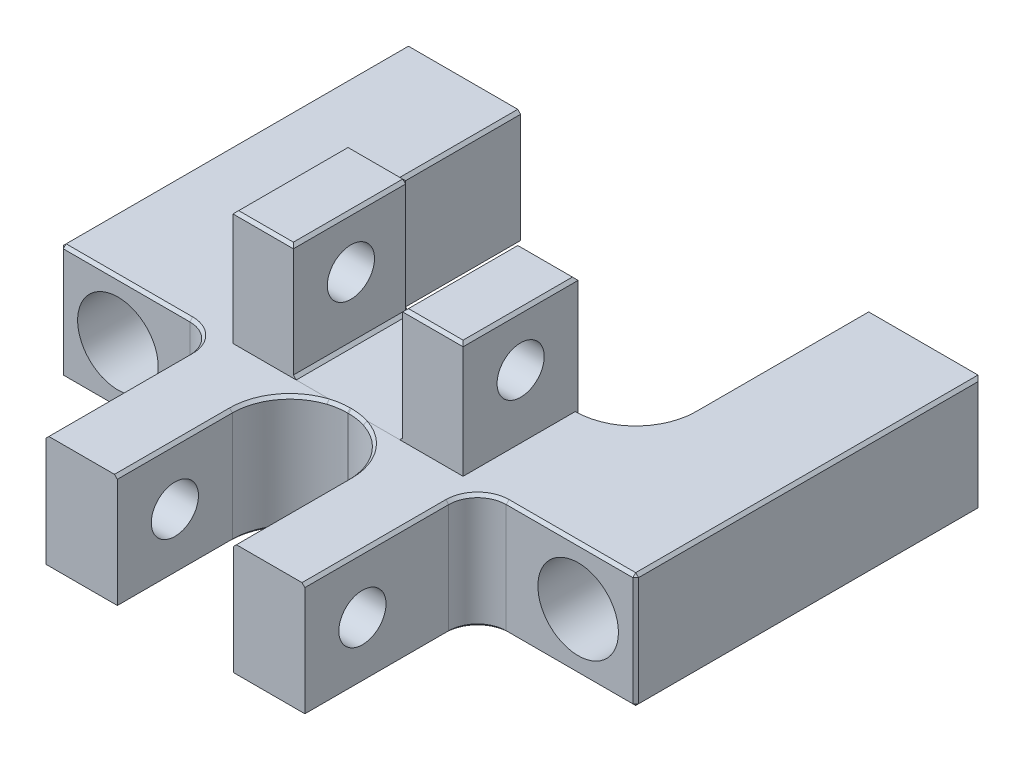
SolidWorks part; units mm, degrees
ref_plane "Front Plane" through (0, 0, 0) normal (0, 0, 1) x (1, 0, 0)
ref_plane "Top Plane" through (0, 0, 0) normal (0, 1, 0) x (1, 0, 0)
ref_plane "Right Plane" through (0, 0, 0) normal (1, 0, 0) x (0, 0, -1)
sketch "Sketch1" plane through (0, 0, 0) normal (0, 0, 1) x (1, 0, 0)
  line L0 (0, 0) -> (40, 0) construction
  line L1 (-50, -10) -> (50, -10)
  line L2 (-50, -10) -> (-50, 10)
  line L3 (-50, 10) -> (50, 10)
  line L4 (50, -10) -> (50, 10)
  line L5 (-50, -10) -> (50, 10) construction
  line L6 (-50, 10) -> (50, -10) construction
  line L7 (0, 0) -> (-40, 0) construction
  circle A0 centre (-40, 0) radius 3.15
  circle A1 centre (40, 0) radius 3.15
  point P0 (0, 0)
  dimension "D4" = 6.3
  dimension "D2" = 10
  dimension "D1" = 20
  dimension "D3" = 40
  dimension "D5" = 100
extrude "Boss-Extrude1" add sketch "Sketch1" along normal blind 20
sketch "Sketch8" plane through (0, 10, 0) normal (0, 1, 0) x (1, 0, 0)
  line L0 (50, 0) -> (-50, 0) construction
  line L1 (-20, 0) -> (20, 0)
  line L2 (-20, 0) -> (-20, -20)
  line L3 (-20, -20) -> (20, -20)
  line L4 (20, 0) -> (20, -20)
  line L5 (50, -20) -> (-50, -20) construction
  line L6 (0, 0) -> (0, -20) construction
  dimension "D1" = 40
  dimension "D2" = 20
extrude "Boss-Extrude2" add sketch "Sketch8" along normal blind 20
sketch "Sketch9" plane through (0, 30, 0) normal (0, 1, 0) x (1, 0, 0)
  line L0 (-20, -20) -> (20, -20) construction
  line L1 (-9.5, 20) -> (9.5, 20)
  line L2 (-9.5, 20) -> (-9.5, -20)
  line L3 (-9.5, -20) -> (9.5, -20)
  line L4 (9.5, 20) -> (9.5, -20)
  line L5 (-9.5, 20) -> (9.5, -20) construction
  line L6 (-9.5, -20) -> (9.5, 20) construction
  point P0 (0, 0)
  dimension "D1" = 19
extrude "Cut-Extrude5" cut sketch "Sketch9" against normal blind 20
sketch "Sketch10" plane through (20, 0, 0) normal (1, 0, 0) x (0, 0, -1)
  line L0 (-10, 30) -> (-10, 21) construction
  line L1 (-20, 30) -> (0, 30) construction
  circle A0 centre (-10, 21) radius 4.1
  dimension "D2" = 8.2
  dimension "D1" = 9
extrude "Cut-Extrude6" cut sketch "Sketch10" against normal through all
sketch "Sketch11" plane through (0, 0, 20) normal (0, 0, 1) x (1, 0, 0)
  line L0 (-20, 10) -> (-50, 10) construction
  line L1 (-22.5, 10) -> (-10.1, 10)
  line L2 (-22.5, 10) -> (-22.5, -10)
  line L3 (-22.5, -10) -> (-10.1, -10)
  line L4 (-10.1, 10) -> (-10.1, -10)
  line L5 (-50, -10) -> (50, -10) construction
  line L6 (50, 10) -> (20, 10) construction
  line L7 (22.5, 10) -> (10.1, 10)
  line L8 (22.5, 10) -> (22.5, -10)
  line L9 (22.5, -10) -> (10.1, -10)
  line L10 (10.1, 10) -> (10.1, -10)
  line L11 (-10.1, 0) -> (10.1, 0) construction
  dimension "D1" = 20.2
  dimension "D2" = 45
extrude "Boss-Extrude3" add sketch "Sketch11" along normal blind 30
fillet "Fillet1" radius 10 2 edges at (10.1, 0, 20) (-10.1, 0, 20)
fillet "Fillet2" radius 5 2 edges at (-22.5, 0, 20) (22.5, 0, 20)
sketch "Sketch12" plane through (22.5, 0, 0) normal (1, 0, 0) x (0, 0, -1)
  line L0 (-50, 0) -> (-40, 0) construction
  line L1 (-50, -10) -> (-50, 10) construction
  circle A0 centre (-40, 0) radius 4.1
  circle A1 centre (-10, 21) radius 4.1 construction
  dimension "D1" = 10
extrude "Cut-Extrude7" cut sketch "Sketch12" against normal through all
sketch "Sketch13" plane through (0, 0, 0) normal (0, 0, -1) x (-1, 0, 0)
  line L0 (50, 10) -> (50, -10) construction
  line L1 (-30, -10) -> (-50, -10)
  line L2 (-30, -10) -> (-30, 10)
  line L3 (-30, 10) -> (-50, 10)
  line L4 (-50, -10) -> (-50, 10)
  line L5 (-30, -10) -> (-50, 10) construction
  line L6 (-30, 10) -> (-50, -10) construction
  line L7 (30, -10) -> (50, -10)
  line L8 (30, -10) -> (30, 10)
  line L9 (30, 10) -> (50, 10)
  line L10 (50, -10) -> (50, 10)
  line L11 (30, -10) -> (50, 10) construction
  line L12 (30, 10) -> (50, -10) construction
  circle A0 centre (-40, 0) radius 3.15 construction
  circle A1 centre (-40, 0) radius 3.15
  circle A2 centre (40, 0) radius 3.15 construction
  circle A3 centre (40, 0) radius 3.15
  point P0 (-40, 0)
  point P7 (40, 0)
extrude "Boss-Extrude4" add sketch "Sketch13" along normal blind 40
fillet "Fillet3" radius 10 2 edges at (-30, 0, 0) (30, 0, 0)
chamfer "Chamfer1" distance 0.5 angle 45 53 edges at (-7.1711, -10, 22.9289) (-50, 0, 20) (38.75, -10, 20) (-23.9645, -10, 21.4645) (-23.9645, 10, 21.4645) (23.9645, 10, 21.4645) (23.9645, -10, 21.4645) (50, 0, -40) (40, -10, -40) (30, -10, -25) (30, 10, -25) (-50, 0, -40) (-40, -10, -40) (-38.75, -10, 20) (-30, 10, -25) (-30, -10, -25) (0, -10, 0) (-27.0711, -10, -2.9289) (-27.0711, 10, -2.9289) (27.0711, 10, -2.9289) (27.0711, -10, -2.9289) (-20, 30, 10) (-14.75, 30, 20) (20, 30, 10) (14.75, 30, 0) (14.75, 30, 20) (-14.75, 30, 0) (-9.5, 30, 10) (0, 10, 0) (9.5, 20, 0) (-9.5, 20, 0) (9.5, 10, 10) (-9.5, 10, 10) (9.5, 30, 10) (50, 0, 20) (-22.5, 10, 37.5) (-22.5, -10, 37.5) (-10.1, -10, 40) (-10.1, 10, 40) (-16.3, -10, 50) (50, -10, -10) (-50, -10, -10) (22.5, -10, 37.5) (-50, 10, -10) (22.5, 10, 37.5) (10.1, 10, 40) (50, 10, -10) (10.1, -10, 40) (16.3, -10, 50) (0, -10, 20) (7.1711, -10, 22.9289) (7.1711, 10, 22.9289) (-7.1711, 10, 22.9289)
sketch "Sketch5" plane through (0, 0, 20) normal (0, 0, 1) x (1, 0, 0)
  circle A0 centre (-40, 0) radius 7
  circle A1 centre (40, 0) radius 7
  dimension "D1" = 14
extrude "Cut-Extrude3" cut sketch "Sketch5" against normal blind 50
